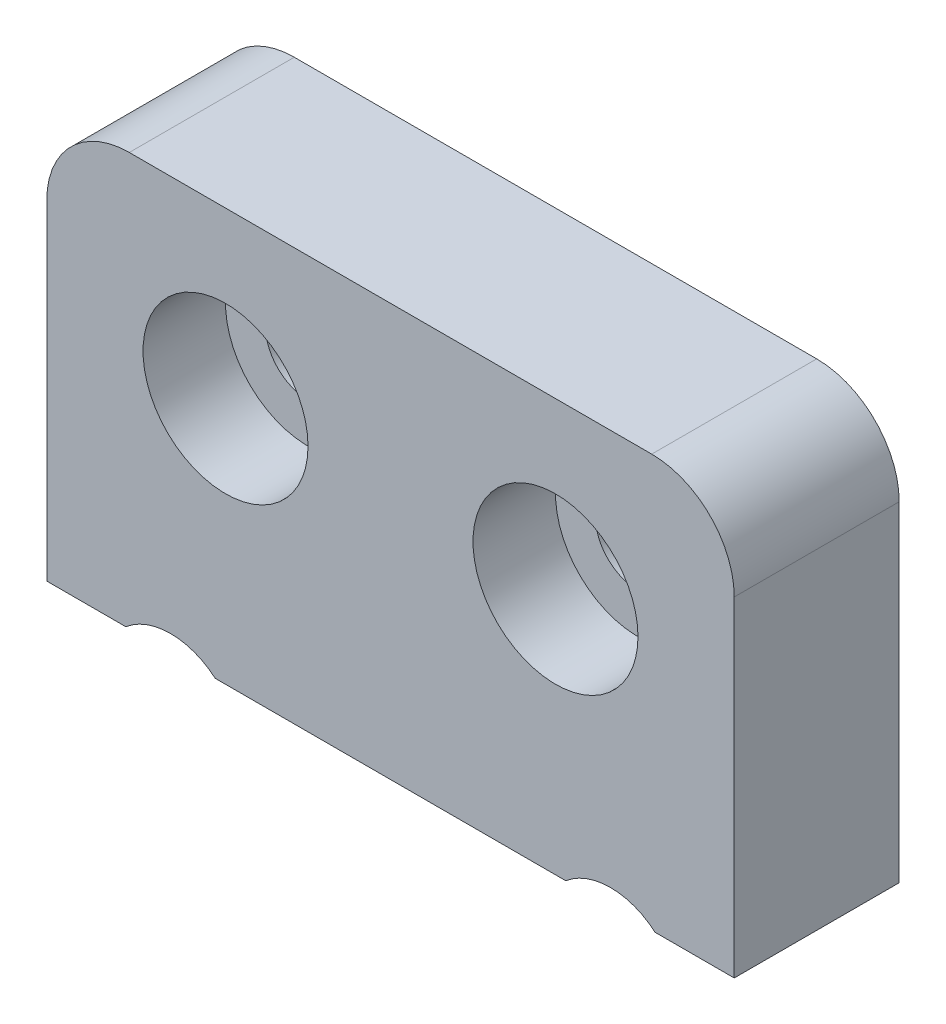
SolidWorks part; units mm, degrees
ref_plane "正面" through (0, 0, 0) normal (0, 0, 1) x (1, 0, 0)
ref_plane "平面" through (0, 0, 0) normal (0, 1, 0) x (1, 0, 0)
ref_plane "右側面" through (0, 0, 0) normal (1, 0, 0) x (0, 0, -1)
sketch "ｽｹｯﾁ1" plane through (0, 0, 0) normal (0, 0, 1) x (1, 0, 0)
  line L0 (12.5, 15) -> (12.5, 0) construction
  line L1 (0, 0) -> (25, 0)
  line L2 (0, 0) -> (0, 15)
  line L3 (0, 15) -> (25, 15)
  line L4 (25, 0) -> (25, 15)
  circle A0 centre (6.5, 9) radius 1.55
  circle A1 centre (18.5, 9) radius 1.55
  dimension "D2" = 12
  dimension "D3" = 3.1
  dimension "D4" = 9
  dimension "D1" = 25
  dimension "D5" = 15
extrude "ﾎﾞｽ - 押し出し1" add sketch "ｽｹｯﾁ1" along normal blind 6
sketch "ｽｹｯﾁ3" plane through (0, 0, 0) normal (0, -1, 0) x (1, 0, 0)
  line L0 (12.5, 6) -> (12.5, 0) construction
  line L1 (0, 6) -> (25, 6) construction
  line L2 (0, 0) -> (25, 0) construction
  line L3 (4.5, 3) -> (12.5, 3) construction
  circle A0 centre (4.5, 3) radius 1.5
  circle A1 centre (20.5, 3) radius 1.5
  dimension "D1" = 16
  dimension "D2" = 3
extrude "ｶｯﾄ - 押し出し1" cut sketch "ｽｹｯﾁ3" against normal blind 6
sketch "ｽｹｯﾁ4" plane through (0, 0, 6) normal (0, 0, 1) x (1, 0, 0)
  line L0 (12.5, 15) -> (12.5, 0) construction
  line L1 (25, 15) -> (0, 15) construction
  line L2 (0, 0) -> (25, 0) construction
  line L3 (4.5, -1.9) -> (4.5, 0) construction
  line L4 (2.8752, 0) -> (6.1248, 0)
  line L5 (22.1248, 0) -> (18.8752, 0)
  arc A0 (2.8752, 0) -> (6.1248, 0) centre (4.5, -1.9) cw
  arc A1 (22.1248, 0) -> (18.8752, 0) centre (20.5, -1.9) ccw
  dimension "D1" = 8
  dimension "D2" = 2.5
  dimension "D3" = 1.9
extrude "ｶｯﾄ - 押し出し2" cut sketch "ｽｹｯﾁ4" against normal through all
fillet "ﾌｨﾚｯﾄ1" radius 3 2 edges at (0, 15, 3) (25, 15, 3)
sketch "ｽｹｯﾁ5" plane through (0, 0, 6) normal (0, 0, 1) x (1, 0, 0)
  circle A0 centre (6.5, 9) radius 3
  circle A1 centre (18.5, 9) radius 3
  dimension "D1" = 6
extrude "ｶｯﾄ - 押し出し3" cut sketch "ｽｹｯﾁ5" against normal blind 3
